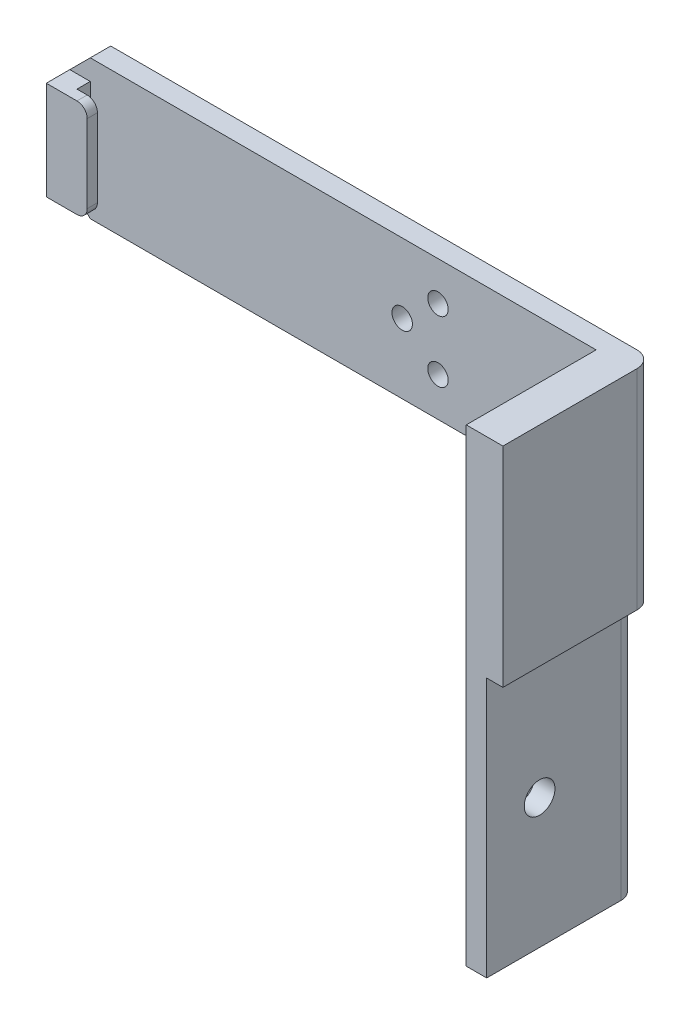
SolidWorks part; units mm, degrees
ref_plane "Front Plane" through (0, 0, 0) normal (0, 0, 1) x (1, 0, 0)
ref_plane "Top Plane" through (0, 0, 0) normal (0, 1, 0) x (1, 0, 0)
ref_plane "Right Plane" through (0, 0, 0) normal (1, 0, 0) x (0, 0, -1)
sketch "Sketch1" plane through (0, 0, 0) normal (0, 0, 1) x (1, 0, 0)
  line L0 (0, 0) -> (81.525, 0)
  line L2 (0, 0) -> (0, 27.25)
  line L3 (0, 27.25) -> (106.925, 27.25)
  line L4 (106.925, -64.425) -> (106.925, 27.25)
  line L5 (81.525, 0) -> (81.525, -64.425)
  line L6 (81.525, -64.425) -> (106.925, -64.425)
  circle A0 centre (72, 19.625) radius 2
  circle A1 centre (72, 7.625) radius 2
  circle A2 centre (65, 13.625) radius 2
  dimension "D7" = 4
  dimension "D1" = 27.25
  dimension "D3" = 12
  dimension "D4" = 6
  dimension "D5" = 7
  dimension "D8" = 34.925
  dimension "D2" = 65
  dimension "D6" = 7.625
  dimension "D9" = 25.4
  dimension "D10" = 64.425
extrude "ProfileBoss-Extrude1" add sketch "Sketch1" along normal blind 4
sketch "Sketch2" plane through (0, 0, 4) normal (0, 0, -1) x (-1, 0, 0)
  line L1 (-106.925, 27.25) -> (-102.925, 27.25)
  line L2 (-106.925, 27.25) -> (-106.925, -64.425)
  line L3 (-106.925, -64.425) -> (-102.925, -64.425)
  line L4 (-102.925, 27.25) -> (-102.925, -64.425)
  line L5 (-81.525, -64.425) -> (-106.925, -64.425) construction
  dimension "D1" = 4
extrude "CornerBoss-Extrude2" add sketch "Sketch2" along normal blind 0.0001 and the other way blind 25.4
sketch "Sketch3" plane through (0, 0, 4) normal (0, 0, -1) x (-1, 0, 0)
  line L1 (0, 23.25) -> (-4, 23.25)
  line L2 (0, 23.25) -> (0, 4)
  line L3 (0, 4) -> (-4, 4)
  line L4 (-4, 23.25) -> (-4, 4)
  line L5 (0, 27.25) -> (0, 0) construction
  line L33 (16.17, 0) -> (-16.17, 0) construction
  point P4 (-106.925, 27.25)
  point P7 (0, 27.25)
  point P10 (-106.925, -26.8659)
  point P11 (-102.925, 27.25)
  point P12 (0, 27.25)
  point P13 (-106.925, 27.25)
  point P14 (-87.1436, -26.8659)
  point P15 (-106.925, -26.8659)
  point P16 (-87.1436, 0)
  point P17 (-87.1436, -26.8659)
  point P18 (0, 0)
  point P19 (-87.1436, 0)
  point P20 (0, 27.25)
  point P21 (0, 0)
  point P22 (-87.1436, -26.8659)
  point P23 (-102.925, -26.8659)
  point P24 (-87.1436, 0)
  point P25 (-87.1436, -26.8659)
  point P26 (0, 0)
  point P27 (-87.1436, 0)
  point P28 (0, 27.25)
  point P29 (0, 0)
  point P30 (-72, 19.625)
  point P31 (-70.0874, 20.2097)
  point P32 (-72, 19.625)
  point P33 (-70.0874, 20.2097)
  point P34 (-72, 7.625)
  point P35 (-70.0874, 8.2097)
  point P36 (-72, 7.625)
  point P37 (-70.0874, 8.2097)
  point P38 (-65, 13.625)
  point P39 (-63.0874, 14.2097)
  point P40 (-65, 13.625)
  point P41 (-63.0874, 14.2097)
  point P42 (-102.925, 27.25)
  point P43 (-106.925, 27.25)
  point P44 (-102.925, -26.8659)
  point P45 (-102.925, 27.25)
  point P46 (-106.925, -26.8659)
  point P47 (-102.925, -26.8659)
  point P48 (-106.925, 27.25)
  point P49 (-106.925, -26.8659)
  point P50 (-102.925, -26.8659)
  point P51 (-102.925, 27.25)
  point P52 (0, 0)
  point P53 (-87.1436, 0)
  point P54 (0, 0)
  point P55 (0, 27.25)
  point P56 (0, 27.25)
  point P57 (-106.925, 27.25)
  point P58 (-106.925, -26.8659)
  point P59 (-106.925, 27.25)
  point P60 (-87.1436, 0)
  point P61 (-87.1436, -26.8659)
  point P62 (-87.1436, -26.8659)
  point P63 (-106.925, -26.8659)
  point P64 (-106.925, 27.25)
  point P65 (-102.925, 27.25)
  point P66 (-106.925, 27.25)
  point P67 (-106.925, -26.8659)
  point P68 (-106.925, -26.8659)
  point P69 (-102.925, -26.8659)
  point P70 (-102.925, 27.25)
  point P71 (-102.925, -26.8659)
  point P72 (-87.1436, -26.8659)
  point P73 (-106.925, -26.8659)
  dimension "D1" = 4
  dimension "D2" = 4
extrude "Boss-Extrude3" add sketch "Sketch3" along normal blind 0.0001 and the other way blind 2.6
sketch "Sketch5" plane through (0, 0, 6.6) normal (0, 0, -1) x (-1, 0, 0)
  line L1 (0, 23.25) -> (-8, 23.25)
  line L2 (0, 23.25) -> (0, 4)
  line L3 (0, 4) -> (-8, 4)
  line L4 (-8, 23.25) -> (-8, 4)
  dimension "D1" = 8
extrude "Boss-Extrude4" add sketch "Sketch5" along normal blind 0.0001 and the other way blind 2
fillet "Fillet1" radius 2 2 edges at (8, 4, 7.5999) (8, 23.25, 7.5999)
chamfer "Chamfer1" distance 4 angle 45 2 edges at (0, 27.25, 2) (0, 0, 2)
sketch "Sketch6" plane through (102.925, 0, 0) normal (-1, 0, 0) x (0, 0, 1)
  line L0 (4, -64.425) -> (29.4, -64.425) construction
  line L2 (0, 0) -> (0, -64.425) construction
  circle A0 centre (19.05, -39.025) radius 3
  dimension "D3" = 6
  dimension "D1" = 25.4
  dimension "D2" = 19.05
extrude "VSMountHoleCut-Extrude1" cut sketch "Sketch6" against normal up to next
sketch "Sketch7" plane through (106.925, 0, 0) normal (1, 0, 0) x (0, 0, -1)
  line L1 (-29.4, 27.25) -> (0, 27.25)
  line L2 (-29.4, 27.25) -> (-29.4, -13.625)
  line L3 (-29.4, -13.625) -> (0, -13.625)
  line L4 (0, 27.25) -> (0, -13.625)
  line L5 (-29.4, 27.25) -> (-29.4, -64.425) construction
  line L6 (0, -64.425) -> (0, 27.25) construction
  dimension "D1" = 25.4
extrude "ThickSideBoss-Extrude5" add sketch "Sketch7" along normal blind 3.175
fillet "Fillet3" radius 3.175 2 edges at (106.925, -39.025, 0) (110.1, 6.8125, 0)
equation "\"DragLinkHeight\"= 27.25mm"
equation "\"FrontOrBackRailLength\"= 20.5in"
equation "\"DragLinkMountHoleDiameter\"= 4mm"
equation "\"MiddleSideHole\"= 5mm"
equation "\"D7@Sketch1\"=\"DragLinkMountHoleDiameter\""
equation "\"VSWidth\"= 1.25in'Spec"
equation "\"RailThickness\"= .125in'Spec"
equation "\"D1@CornerBoss-Extrude2\"=.00001"
equation "\"HangerThickness\"= 4mm"
equation "\"D1@ProfileBoss-Extrude1\"=\"HangerThickness\""
equation "\"D1@Sketch2\"=\"HangerThickness\""
equation "\"HangerClipWidth\"= 2.6mm"
equation "\"D1@Boss-Extrude3\"=\"HangerClipWidth\""
equation "\"D2@Sketch3\"=\"HangerThickness\""
equation "\"D1@Sketch3\"=\"HangerThickness\""
equation "\"D1@Sketch5\"=\"HangerThickness\"*2"
equation "\"D1@Boss-Extrude4\"=\"HangerThickness\"/2"
equation "\"D1@Chamfer1\"=\"HangerThickness\""
equation "\"D1@Sketch6\"=\"MidLeftOrRightRailHeight\"/2"
equation "\"GapBetweenVerticalSupportsAndRails\"= \"RailThickness\" * 2"
equation "\"FrameFastenerHoleOffsetFromSide\"= \"VSWidth\" / 2 + \"GapBetweenVerticalSupportsAndRails\""
equation "\"D6@Sketch1\"=(\"DragLinkHeight\"-12)/2"
equation "\"D9@Sketch1\"=\"VSWidth\"-\"RailThickness\"*2"
equation "\"M6ScrewDiameter\"= 6mm"
equation "\"D3@Sketch6\"=\"M6ScrewDiameter\""
equation "\"D1@ThickSideBoss-Extrude5\" = \"RailThickness\""
equation "\"MidLeftOrRightRailHeight\"= 2.0in"
equation "\"D1@Sketch7\"=\"MidLeftOrRightRailHeight\"/2"
equation "\"HangerRiseHeight\"= 20mm - 6.375"
equation "\"D10@Sketch1\"=\"MidLeftOrRightRailHeight\" + \"HangerRiseHeight\""
equation "\"D2@CornerBoss-Extrude2\"=\"VSWidth\" - \"RailThickness\"*2"
equation "\"D2@Boss-Extrude3\"=\"HangerClipWidth\""
equation "\"D2@Sketch6\"=\"FrameFastenerHoleOffsetFromSide\" - \"RailThickness\""
equation "\"D2@Boss-Extrude4\"=\"HangerThickness\"/2"
